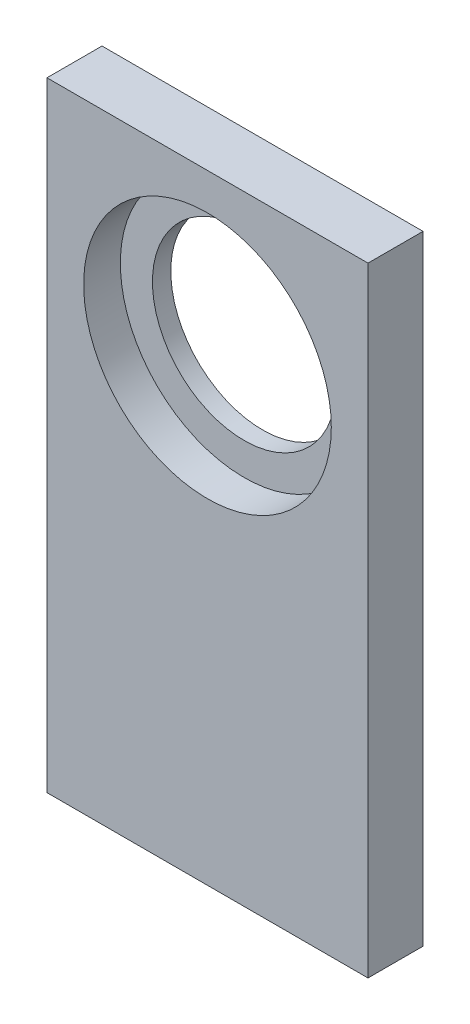
SolidWorks part; units mm, degrees
ref_plane "Front Plane" through (0, 0, 0) normal (0, 0, 1) x (1, 0, 0)
ref_plane "Top Plane" through (0, 0, 0) normal (0, 1, 0) x (1, 0, 0)
ref_plane "Right Plane" through (0, 0, 0) normal (1, 0, 0) x (0, 0, -1)
sketch "Sketch1" plane through (0, 0, 0) normal (0, 0, 1) x (1, 0, 0)
  line L0 (-17.5, 25) -> (-17.5, 42.5)
  line L1 (-17.5, -25) -> (17.5, -25)
  line L2 (-17.5, -25) -> (-17.5, 25)
  line L4 (17.5, -25) -> (17.5, 25)
  line L5 (-17.5, -25) -> (0, 0) construction
  line L6 (0, 0) -> (17.5, -25) construction
  line L7 (-17.5, 42.5) -> (17.5, 42.5)
  line L8 (17.5, 42.5) -> (17.5, 25)
  point P0 (0, 0)
  dimension "D1" = 50
  dimension "D2" = 35
extrude "Boss-Extrude1" add sketch "Sketch1" along normal blind 6
sketch "Sketch4" plane through (0, 0, 6) normal (0, 0, 1) x (1, 0, 0)
  line L0 (0, -25) -> (0, 25) construction
  line L2 (-17.5, -25) -> (17.5, -25) construction
  circle A1 centre (0, 25) radius 13.5
  dimension "D1" = 50
  dimension "D2" = 27
extrude "Cut-Extrude1" cut sketch "Sketch4" against normal blind 4
sketch "Sketch5" plane through (0, 0, 2) normal (0, 0, 1) x (1, 0, 0)
  circle A1 centre (0, 25) radius 10
  dimension "D1" = 20
extrude "Cut-Extrude2" cut sketch "Sketch5" against normal through all
